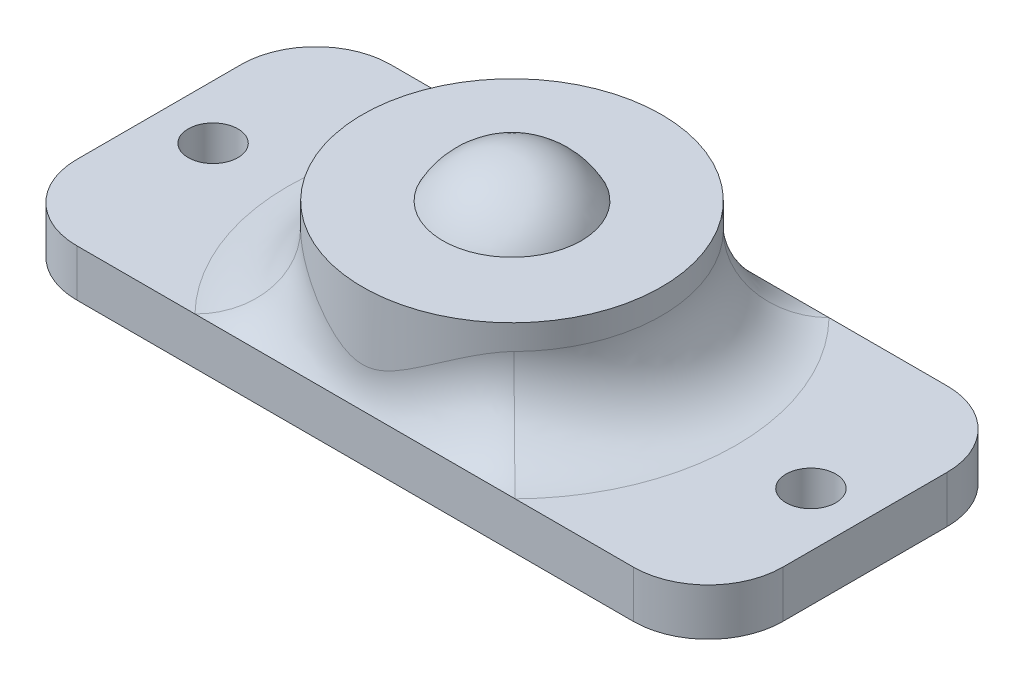
SolidWorks part; units mm, degrees
material "Nylon 101"
ref_plane "Front" through (0, 0, 0) normal (0, 0, 1) x (1, 0, 0)
ref_plane "Top" through (0, 0, 0) normal (0, 1, 0) x (1, 0, 0)
ref_plane "Right" through (0, 0, 0) normal (1, 0, 0) x (0, 0, -1)
sketch "Sketch1" plane through (0, 0, 0) normal (0, 0, 1) x (1, 0, 0)
  line L0 (0, 0) -> (0, 12) construction
  line L1 (0, 12) -> (0, 2) construction
  line L2 (0, 12) -> (0, 2)
  line L3 (-22.5, 3) -> (22.5, 3)
  line L4 (-22.5, 3) -> (-22.5, 0)
  line L5 (-22.5, 0) -> (22.5, 0)
  line L6 (22.5, 3) -> (22.5, 0)
  line L7 (-9.525, 3) -> (9.525, 3)
  line L8 (-9.525, 3) -> (-9.525, 9.35)
  line L9 (-9.525, 9.35) -> (9.525, 9.35)
  line L10 (9.525, 3) -> (9.525, 9.35)
  arc A0 (0, 2) -> (0, 12) centre (0, 7) ccw
  dimension "D1" = 12
  dimension "D2" = 10
  dimension "D3" = 45
  dimension "D4" = 3
  dimension "D5" = 19.05
  dimension "D6" = 6.35
extrude "Boss-Extrude1" add sketch "Sketch1" along normal mid plane 20 contours L6 L3 L7 L4 L5 | L2 A0 L3 region at (1.1417, 2.5964, 0) region at (-0.0175, 1.4831, 0)
revolve "Revolve1" add sketch "Sketch1<5>" angle 360 about L0 region at (7.0118, 6.0426, 0)
sketch "Sketch1<5>" plane through (0, 0, 0) normal (0, 0, 1) x (1, 0, 0) same geometry as "Sketch1"
revolve "Revolve2" add sketch "Sketch1<7>" angle 360 about L2 region at (1.7346, 10.4385, 0) region at (2.3032, 6.3198, 0)
sketch "Sketch1<7>" plane through (0, 0, 0) normal (0, 0, 1) x (1, 0, 0) same geometry as "Sketch1"
sketch "Sketch3" plane through (0, 3, 0) normal (0, 1, 0) x (1, 0, 0)
  line L0 (-19.05, 0) -> (19.05, 0)
  circle A0 centre (-19.05, 0) radius 1.5875
  circle A1 centre (19.05, 0) radius 1.5875
  point P4 (0, 0)
  dimension "D2" = 3.175
  dimension "D1" = 38.1
extrude "Cut-Extrude1" cut sketch "Sketch3" against normal through all contours A0 | A1 region at (19.05, 3, -1.5426) region at (-20.5926, 3, 0)
fillet "Fillet1" radius 4.7625 5 edges at (22.5, 1.5, 10) (-22.5, 1.5, 10) (-22.5, 1.5, -10) (22.5, 1.5, -10) (0, 3, -9.525)
